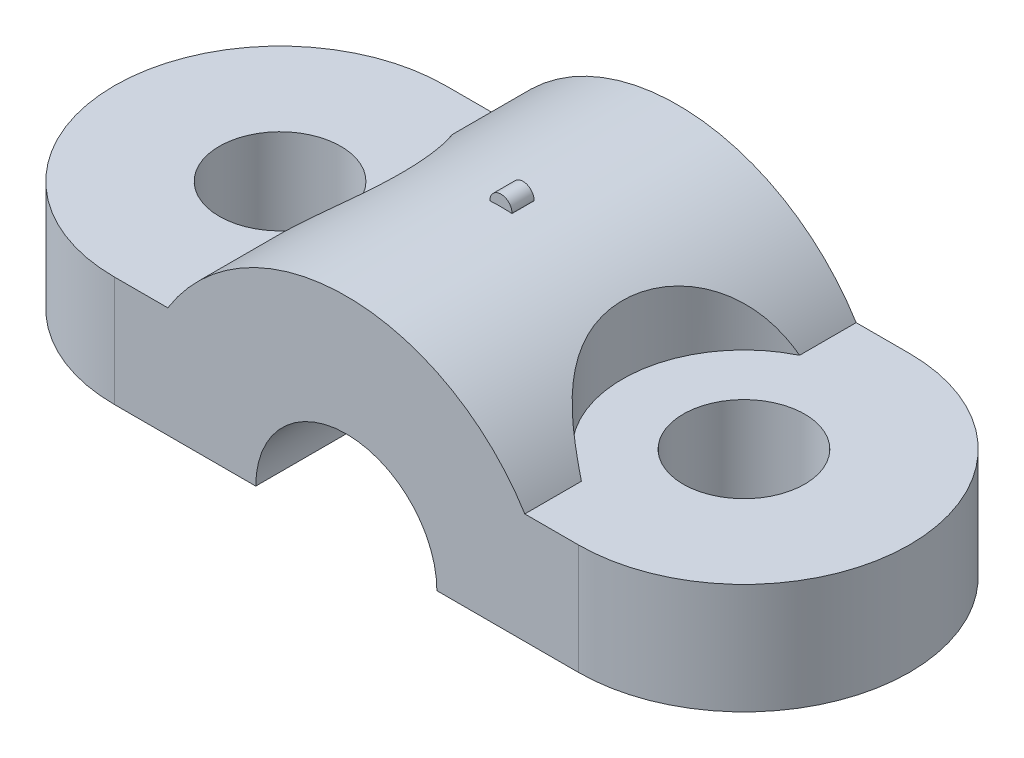
SolidWorks part; units mm, degrees
material "ABS"
ref_plane "Front Plane" through (0, 0, 0) normal (0, 0, 1) x (1, 0, 0)
ref_plane "Top Plane" through (0, 0, 0) normal (0, 1, 0) x (1, 0, 0)
ref_plane "Right Plane" through (0, 0, 0) normal (1, 0, 0) x (0, 0, -1)
sketch "Sketch1" plane through (0, 0, 0) normal (0, 1, 0) x (1, 0, 0)
  line L0 (-11, 7.5) -> (10, 7.5)
  line L1 (-11, -7.5) -> (10, -7.5)
  line L2 (-8.58, 7.5) -> (-8.58, 4.939)
  line L3 (-8.58, -4.939) -> (-8.58, -7.5)
  line L4 (7.58, -7.5) -> (7.58, -4.939)
  line L5 (7.58, 7.5) -> (7.58, 4.939)
  circle A0 centre (-11, 0) radius 2.75
  circle A1 centre (10, 0) radius 2.75
  circle A2 centre (-11, 0) radius 5.5
  circle A3 centre (10, 0) radius 5.5
  circle A4 centre (-11, 0) radius 7.5
  circle A5 centre (10, 0) radius 7.5
  point P21 (-0.5, 7.5)
  dimension "D1" = 5.5
  dimension "D2" = 2.75
  dimension "D3" = 4.75
  dimension "D4" = 21
  dimension "D5" = 10
  dimension "D6" = 8.08
  dimension "D7" = 8.08
extrude "Boss-Extrude1" add sketch "Sketch1" along normal blind 9.5 contours A5 L5 L0 L2 A4 L3 L1 L4 | L3 A4 L2 A2 | L5 A5 L4 A3 region at (-0.5, 0, 0) region at (-5.0234, 0, -4.2769) region at (7.4292, 0, -6.0189)
extrude "Boss-Extrude2" add sketch "Sketch1<3>" along normal blind 5 contours A2 A0 | A4 L3 A2 L2 | A3 A1 | A5 L5 A3 L4 | A4 L2 L0 | A4 L1 L3 | A5 L4 L1 | A5 L0 L5 region at (-9.8029, 0, -7.2216) region at (-9.1817, 0, -7.3802) region at (-9.1817, 0, 7.3802) region at (8.1817, 0, -7.3802) region at (-6.4651, 0, -2.828) region at (15.1761, 0, -5.1761) region at (8.1817, 0, 7.3802) region at (12.828, 0, -4.5349)
sketch "Sketch1<3>" plane through (0, 0, 0) normal (0, 1, 0) x (1, 0, 0) same geometry as "Sketch1"
sketch "Sketch3" plane through (0, 0, 7.5) normal (0, 0, 1) x (1, 0, 0)
  line L0 (-11, 0) -> (10, 0) construction
  line L3 (-8.58, 9.5) -> (-8.58, 5) construction
  line L4 (-8.58, 9.5) -> (7.58, 9.5) construction
  line L5 (7.58, 9.5) -> (7.58, 5) construction
  line L6 (-8.58, 9.5) -> (-8.58, 5)
  line L7 (-8.58, 9.5) -> (7.58, 9.5)
  line L8 (7.58, 9.5) -> (7.58, 5)
  circle A0 centre (-0.5, 0) radius 4.1
  arc A1 (-8.58, 5) -> (7.58, 5) centre (-0.5, -0.004) cw
  point P6 (-0.5, 0)
  line M1 (-11, 0) -> (10, 0)
  line M4 (7.58, 9.5) -> (-8.58, 9.5)
  line M10 (7.58, 5) -> (7.58, 9.5)
  line M11 (-8.58, 9.5) -> (-8.58, 5)
  dimension "D2" = 8.2
  dimension "D1" = 0
extrude "Cut-Extrude2" cut sketch "Sketch3" against normal through all contours A1 L7 M11 | A1 M4 M10 | A0 M1 region at (-6.6679, 8.2305, 7.5) region at (5.6679, 8.2305, 7.5) region at (-0.5, 1.7401, 7.5)
sketch "Sketch5" plane through (0, 5, 0) normal (0, 1, 0) x (1, 0, 0)
  line L0 (-18.5, 0) -> (17.5, 0) construction
  arc A0 (-11, 7.5) -> (-11, -7.5) centre (-11, 0) ccw construction
  arc A1 (10, -7.5) -> (10, 7.5) centre (10, 0) ccw construction
sketch "Sketch6" plane through (0, 0, 0) normal (0, -1, 0) x (1, 0, 0)
  line L0 (-18.5, 0) -> (17.5, 0) construction
  arc A0 (-11, 7.5) -> (-11, -7.5) centre (-11, 0) ccw construction
  arc A1 (10, -7.5) -> (10, 7.5) centre (10, 0) ccw construction
sketch3d "3DSketch1"
  line L0 (-18.5, 0, 0) -> (17.5, 0, 0) construction
  line L1 (-18.5, 5, 0) -> (17.5, 5, 0) construction
sketch "Sketch7" plane through (0, 0, 0) normal (0, 0, 1) x (1, 0, 0)
  line L0 (0, 0) -> (0, 15.6574) construction
  arc A0 (7.58, 5) -> (-8.58, 5) centre (-0.5, -0.004) ccw construction
  arc A1 (7.58, 5) -> (-8.58, 5) centre (-0.5, -0.004) ccw
  circle A2 centre (-0.5, 9.5) radius 0.5
  dimension "D1" = 1
extrude "Boss-Extrude3" add sketch "Sketch7" along normal mid plane 1 contours A1 L0 A2 | L0 A1 A2 region at (-0.5, 9.7098, 0)
